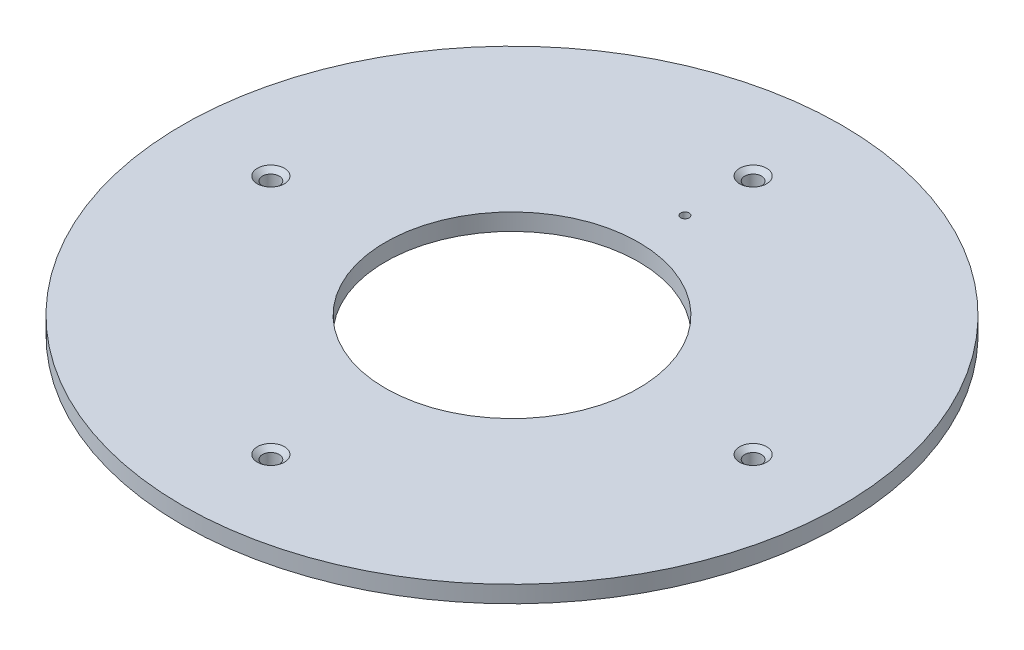
SolidWorks part; units mm, degrees
material "1060 Alloy"
ref_plane "Front Plane" through (0, 0, 0) normal (0, 0, 1) x (1, 0, 0)
ref_plane "Top Plane" through (0, 0, 0) normal (0, 1, 0) x (1, 0, 0)
ref_plane "Right Plane" through (0, 0, 0) normal (1, 0, 0) x (0, 0, -1)
sketch "Sketch1" plane through (0, 0, 0) normal (0, 1, 0) x (1, 0, 0)
  circle A0 centre (0, 0) radius 19.53
  dimension "D1" = 39.06
extrude "Boss-Extrude1" add sketch "Sketch1" along normal blind 1
sketch "Sketch2" plane through (0, 1, 0) normal (0, 1, 0) x (1, 0, 0)
  circle A0 centre (0, 0) radius 7.5
  dimension "D1" = 15
extrude "Cut-Extrude1" cut sketch "Sketch2" against normal through all both and the other way through all
ref_plane "Plane2" through (0, 0.5, 0) normal (0, 1, 0) x (1, 0, 0)
sketch "Sketch4" plane through (0, 1, 0) normal (0, 1, 0) x (1, 0, 0)
  circle A0 centre (0, 10.25) radius 0.25
  dimension "D1" = 0.5
  dimension "D2" = 10.25
extrude "Cut-Extrude2" cut sketch "Sketch4" against normal through all both and the other way through all
hole_wizard "CSK for M2 Flat Head Machine Screw1" positions "Sketch5" profile "Sketch6" countersink size "M2" standard "ANSI Metric" end condition through all
sketch "Sketch5" plane through (0, 1, 0) normal (0, 1, 0) x (1, 0, 0)
  point P0 (0, 14.29)
  point P2 (14.29, 0)
  point P4 (0, -14.29)
  point P6 (-14.29, 0)
  dimension "D1" = 14.29
  dimension "D2" = 14.29
  dimension "D3" = 14.29
  dimension "D4" = 14.29
sketch "Sketch6" plane through (0, 1, -14.29) normal (1, 0, 0) x (0, 0, 1)
  line L0 (0, 0) -> (0, 1)
  line L1 (0, 1) -> (0.5, 1)
  line L2 (0.5, 1) -> (0.5, 0.2517)
  line L3 (0.5, 0.2517) -> (0.8, 0)
  line L5 (0.8, 0) -> (0, 0)
  line L6 (-0.5, 0.2517) -> (-0.8, 0) construction
  line L11 (0, -6.35) -> (0, 107.95) construction
  dimension "Thru Hole Dia." = 1
  dimension "Thru Hole Depth" = 1
  dimension "Near C'Sink Dia." = 1.6
  dimension "Near C'Sink Angle" = 100
